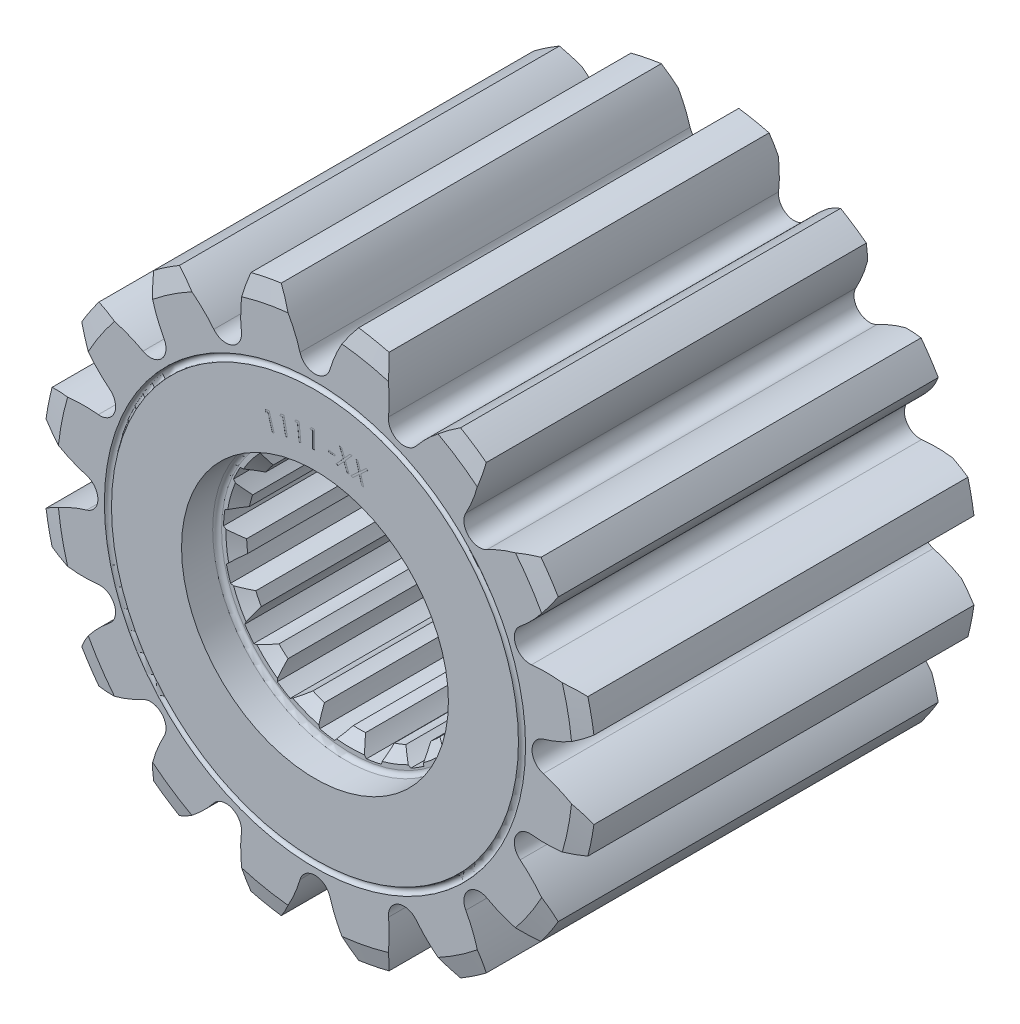
SolidWorks part; units mm, degrees
material "EN39B"
ref_plane "Front Plane" through (0, 0, 0) normal (0, 0, 1) x (1, 0, 0)
ref_plane "Top Plane" through (0, 0, 0) normal (0, 1, 0) x (1, 0, 0)
ref_plane "Right Plane" through (0, 0, 0) normal (1, 0, 0) x (0, 0, -1)
sketch "Sketch2" plane through (0, 0, 0) normal (1, 0, 0) x (0, 0, -1)
  line L0 (0, 15) -> (0, 22.875)
  line L1 (-4, 14.5) -> (-4, 14)
  line L2 (0, 23.675) -> (0, 29)
  line L3 (0, 29) -> (-0.5627, 31.1)
  line L4 (-0.5627, 31.1) -> (-43.2873, 31.1)
  line L5 (0, 15) -> (-3.5, 15)
  line L6 (-39.85, 14) -> (-38.85, 12.69)
  line L7 (-5, 12.69) -> (-38.85, 12.69)
  line L8 (-43.85, 29) -> (-43.2873, 31.1)
  line L9 (-21.925, 53.6422) -> (-21.925, 0) construction
  line L10 (0, 0) -> (-49.8392, 0) construction
  line L11 (-43.85, 23.675) -> (-43.85, 29)
  line L12 (-4, 14) -> (-5, 12.69)
  line L13 (-43.85, 15) -> (-43.85, 22.875)
  line L14 (-43.85, 15) -> (-40.35, 15)
  line L15 (-39.85, 14.5) -> (-39.85, 14)
  arc A0 (0, 23.675) -> (0, 22.875) centre (0, 23.275) ccw
  arc A1 (-43.85, 23.675) -> (-43.85, 22.875) centre (-43.85, 23.275) cw
  arc A2 (-3.5, 15) -> (-4, 14.5) centre (-3.5, 14.5) ccw
  arc A3 (-40.35, 15) -> (-39.85, 14.5) centre (-40.35, 14.5) cw
  point P17 (-21.925, 31.1)
  point P25 (-21.925, 12.69)
  point P28 (-3.9867, 15)
  point P29 (-39.8633, 15)
  dimension "D11" = 28
  dimension "D12" = 0.5
  dimension "D2" = 46.55
  dimension "D5" = 0.4
  dimension "D3" = 4
  dimension "D4" = 30
  dimension "D6" = 62.2
  dimension "D7" = 58
  dimension "D8" = 15
  dimension "D9" = 25.38
  dimension "D10" = 5
  dimension "D13" = 43.85
revolve "Revolve1" add sketch "Sketch2" angle 360 about L10
sketch "Sketch3" plane through (0, 0, 0) normal (0, 0, 1) x (1, 0, 0)
  line L0 (0, 0) -> (0, 38.1308) construction
  arc A0 (4.35, 30.7943) -> (-4.35, 30.7943) centre (0, 0) ccw
  circle A1 centre (0, 0) radius 31.1 construction
  arc A2 (-1.6791, 25.6605) -> (1.6791, 25.6605) centre (0, 26.1535) ccw
  arc A3 (-1.6791, 25.6605) -> (-4.35, 30.7943) centre (-16.0715, 21.4344) ccw
  arc A4 (1.6791, 25.6605) -> (4.35, 30.7943) centre (16.0715, 21.4344) cw
  dimension "D1" = 3.5
  dimension "D3" = 24.4035
  dimension "D4" = 15
  dimension "D2" = 8.7
extrude "Cut-Extrude1" cut sketch "Sketch3" along normal through all
ref_axis "Axis1" through (0, 0, 5) along (0, 0, 1)
pattern_circular "CirPattern1" count 16 over 360 about axis through (0, 0, 5) along (0, 0, 1) of "Cut-Extrude1"
sketch "Sketch4" plane through (0, 0, 0) normal (0, 0, 1) x (1, 0, 0)
  line L0 (0, 0) -> (0, 18.0332) construction
  arc A0 (0.85, 14.2647) -> (-0.85, 14.2647) centre (0, 0) ccw
  arc A1 (1.65, 12.5823) -> (-1.65, 12.5823) centre (0, 0) ccw
  arc A2 (-0.85, 14.2647) -> (-1.65, 12.5823) centre (12.0667, 7.0913) ccw
  circle A3 centre (0, 0) radius 12.69 construction
  arc A4 (0.85, 14.2647) -> (1.65, 12.5823) centre (-12.0667, 7.0913) cw
  dimension "D1" = 28.58
  dimension "D4" = 14.7749
  dimension "D2" = 1.7
  dimension "D3" = 3.3
extrude "Cut-Extrude2" cut sketch "Sketch4" along normal through all
pattern_circular "CirPattern2" count 17 over 360 about axis through (0, 0, 5) along (0, 0, 1) of "Cut-Extrude2"
sketch "Sketch5" plane through (0, 0, 43.85) normal (0, 0, 1) x (1, 0, 0)
  arc A0 (-16.9034, 1.8097) -> (16.8186, 2.4766) centre (0, 0) cw construction
  text T0 " 1111 -XX" font "Century Gothic" height 2
  dimension "D1" = 17
extrude "PARTNO" cut sketch "Sketch5" against normal blind 0.01
